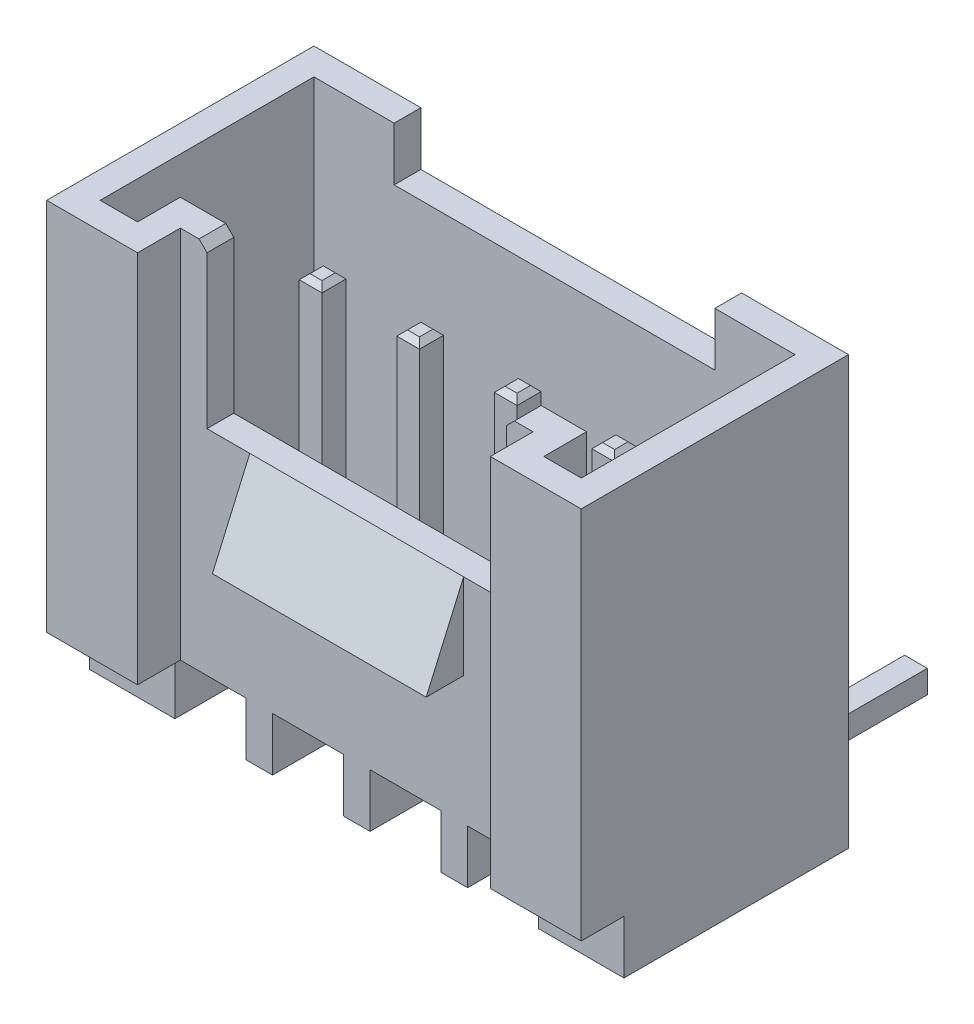
SolidWorks part; units mm, degrees
ref_plane "Plan de face" through (0, 0, 0) normal (0, 0, 1) x (1, 0, 0)
ref_plane "Plan de dessus" through (0, 0, 0) normal (0, 1, 0) x (1, 0, 0)
ref_plane "Plan de droite" through (0, 0, 0) normal (1, 0, 0) x (0, 0, -1)
sketch "Esquisse1" plane through (0, 0, 0) normal (0, 1, 0) x (1, 0, 0)
  line L1 (0, 0) -> (10, 0)
  line L2 (0, 0) -> (0, 5)
  line L3 (0, 5) -> (10, 5)
  line L4 (10, 0) -> (10, 5)
  dimension "D1" = 5
  dimension "D2" = 10
extrude "Boss.-Extru.1" add sketch "Esquisse1" along normal blind 8
sketch "Esquisse2" plane through (0, 8, 0) normal (0, 1, 0) x (1, 0, 0)
  line L0 (0, 0) -> (10, 0) construction
  line L1 (1.7, 0) -> (8.3, 0)
  line L2 (1.7, 0) -> (1.7, 0.8)
  line L3 (1.7, 0.8) -> (8.3, 0.8)
  line L4 (8.3, 0) -> (8.3, 0.8)
  line L5 (0, 5) -> (0, 0) construction
  line L6 (10, 0) -> (10, 5) construction
  dimension "D1" = 1.7
  dimension "D2" = 1.7
  dimension "D3" = 0.8
extrude "Enlèv. mat.-Extru.1" cut sketch "Esquisse2" against normal blind 8
sketch "Esquisse4" plane through (0, 8, 0) normal (0, 1, 0) x (1, 0, 0)
  line L16 (0.5, 0.5) -> (1.2, 0.5)
  line L17 (1.2, 0.5) -> (1.2, 1.3)
  line L18 (1.2, 1.3) -> (8.8, 1.3)
  line L19 (8.8, 1.3) -> (8.8, 0.5)
  line L20 (8.8, 0.5) -> (9.5, 0.5)
  line L21 (9.5, 0.5) -> (9.5, 4.5)
  line L22 (9.5, 4.5) -> (0.5, 4.5)
  line L23 (0.5, 4.5) -> (0.5, 0.5)
  line L24 (0.5, 0.5) -> (1.2, 0.5)
  line L25 (1.2, 0.5) -> (1.2, 1.3)
  line L26 (1.2, 1.3) -> (8.8, 1.3)
  line L27 (8.8, 1.3) -> (8.8, 0.5)
  line L28 (8.8, 0.5) -> (9.5, 0.5)
  line L29 (9.5, 0.5) -> (9.5, 4.5)
  line L30 (9.5, 4.5) -> (0.5, 4.5)
  line L31 (0.5, 4.5) -> (0.5, 0.5)
  dimension "D1" = 0.5
extrude "Enlèv. mat.-Extru.2" cut sketch "Esquisse4" against normal blind 6.5
sketch "Esquisse5" plane through (0, 8, 0) normal (0, 1, 0) x (1, 0, 0)
  line L0 (10, 5) -> (0, 5) construction
  line L1 (2, 5) -> (8, 5)
  line L2 (2, 5) -> (2, 4.5)
  line L3 (2, 4.5) -> (8, 4.5)
  line L4 (8, 5) -> (8, 4.5)
  line L5 (9.5, 4.5) -> (0.5, 4.5) construction
  line L6 (10, 0) -> (10, 5) construction
  line L7 (0, 5) -> (0, 0) construction
  dimension "D1" = 2
  dimension "D2" = 2
extrude "Enlèv. mat.-Extru.3" cut sketch "Esquisse5" against normal blind 1
sketch "Esquisse6" plane through (0, 8, 0) normal (0, 1, 0) x (1, 0, 0)
  line L0 (1.2, 1.3) -> (8.8, 1.3) construction
  line L1 (2.2, 1.3) -> (7.8, 1.3)
  line L2 (2.2, 1.3) -> (2.2, 0.8)
  line L3 (2.2, 0.8) -> (7.8, 0.8)
  line L4 (7.8, 1.3) -> (7.8, 0.8)
  line L5 (8.3, 0.8) -> (1.7, 0.8) construction
  line L6 (10, 0) -> (10, 5) construction
  line L7 (0, 5) -> (0, 0) construction
  dimension "D1" = 2.2
  dimension "D2" = 2.2
extrude "Enlèv. mat.-Extru.4" cut sketch "Esquisse6" against normal blind 3
sketch "Esquisse7" plane through (10, 0, 0) normal (1, 0, 0) x (0, 0, -1)
  line L1 (0, 0) -> (0.8, 0)
  line L2 (0, 0) -> (0, 1)
  line L3 (0, 1) -> (0.8, 1)
  line L4 (0.8, 0) -> (0.8, 1)
  dimension "D1" = 0.8
  dimension "D2" = 1
extrude "Enlèv. mat.-Extru.5" cut sketch "Esquisse7" against normal blind 10
sketch "Esquisse8" plane through (0, 0, 0) normal (0, -1, 0) x (1, 0, 0)
  line L0 (10, -0.8) -> (0, -0.8) construction
  line L1 (1.6, -0.8) -> (8.4, -0.8)
  line L2 (1.6, -0.8) -> (1.6, -5)
  line L3 (1.6, -5) -> (8.4, -5)
  line L4 (8.4, -0.8) -> (8.4, -5)
  line L5 (10, -5) -> (0, -5) construction
  line L6 (0, -5) -> (0, -0.8) construction
  line L7 (10, -0.8) -> (10, -5) construction
  dimension "D1" = 1.6
  dimension "D2" = 1.6
extrude "Enlèv. mat.-Extru.6" cut sketch "Esquisse8" against normal blind 1
sketch "Esquisse9" plane through (1.6, 0, 0) normal (1, 0, 0) x (0, 0, -1)
  line L0 (5, 1) -> (0.8, 1) construction
  line L1 (4.7, 1) -> (3.9, 0.2)
  line L2 (3.9, 0.2) -> (1.9, 0.2)
  line L3 (1.9, 0.2) -> (1.1, 1)
  line L4 (0.8, 0) -> (5, 0) construction
  line L5 (4.7, 1) -> (1.1, 1)
  dimension "D1" = 45
  dimension "D2" = 45
  dimension "D3" = 0.2
  dimension "D4" = 0.3
  dimension "D5" = 0.3
extrude "Boss.-Extru.2" add sketch "Esquisse9" along normal blind 6.8
ref_plane "Plan1" through (5, 0, 0) normal (1, 0, 0) x (0, 0, -1)
sketch "Esquisse11" plane through (5, 0, 0) normal (1, 0, 0) x (0, 0, -1)
  line L0 (0.8, 5) -> (0.1, 3.4)
  line L1 (0.1, 3.4) -> (0.8, 3.4)
  line L2 (0.8, 1) -> (0.8, 8) construction
  line L3 (0.8, 3.4) -> (0.8, 5)
  dimension "D1" = 1.6
  dimension "D2" = 0.7
extrude "Boss.-Extru.3" add sketch "Esquisse11" along normal blind 2 and the other way blind 2
ref_plane "Plan2" through (0, 1, 0) normal (0, 1, 0) x (1, 0, 0)
sketch "Esquisse12" plane through (0, 1, 0) normal (0, 1, 0) x (1, 0, 0)
  line L0 (8.3, 0.8) -> (1.7, 0.8) construction
  line L1 (1.6, 5) -> (8.4, 5) construction
  line L2 (3, 0.8) -> (7, 0.8) construction
  line L3 (4.75, 0.8) -> (5.25, 0.8)
  line L4 (4.75, 0.8) -> (4.75, 5)
  line L5 (4.75, 5) -> (5.25, 5)
  line L6 (5.25, 0.8) -> (5.25, 5)
  line L8 (2.925, 0.8) -> (3.425, 0.8)
  line L9 (2.925, 0.8) -> (2.925, 5)
  line L10 (2.925, 5) -> (3.425, 5)
  line L11 (3.425, 0.8) -> (3.425, 5)
  line L12 (6.575, 0.8) -> (7.075, 0.8)
  line L13 (6.575, 0.8) -> (6.575, 5)
  line L14 (6.575, 5) -> (7.075, 5)
  line L15 (7.075, 0.8) -> (7.075, 5)
  line L16 (3.175, 0.8) -> (3.175, 5) construction
  line L17 (6.825, 0.8) -> (6.825, 5) construction
  point P0 (5, 0.8)
  point P1 (5, 5)
  dimension "D1" = 0.5
  dimension "D2" = 0.25
  dimension "D3" = 0.5
  dimension "D4" = 0.5
  dimension "D5" = 0.25
  dimension "D6" = 0.25
  dimension "D7" = 1.575
  dimension "D8" = 1.575
extrude "Boss.-Extru.4" add sketch "Esquisse12" against normal blind 1
chamfer "Chanfrein1" distance 0.15 angle 45 2 edges at (2.2, 8, -1.05) (7.8, 8, -1.05)
sketch "Esquisse13" plane through (0, 0.2, 0) normal (0, -1, 0) x (1, 0, 0)
  line L0 (5, -0.8) -> (5, -5) construction
  line L1 (2.05, -2.675) -> (2.475, -2.675)
  line L2 (2.05, -2.675) -> (2.05, -3.125)
  line L3 (2.05, -3.125) -> (2.475, -3.125)
  line L4 (2.475, -2.675) -> (2.475, -3.125)
  line L5 (4.3, -3.125) -> (3.875, -3.125)
  line L6 (3.875, -2.675) -> (3.875, -3.125)
  line L7 (4.3, -2.675) -> (4.3, -3.125)
  line L8 (4.3, -2.675) -> (3.875, -2.675)
  line L9 (4.75, -0.8) -> (5.25, -0.8) construction
  line L10 (5.25, -5) -> (4.75, -5) construction
  line L11 (1.6, -0.8) -> (1.6, -5) construction
  line L12 (2.925, -5) -> (2.925, -0.8) construction
  line L14 (2.05, -2.9) -> (2.475, -2.9) construction
  line L15 (2.925, -1.9) -> (1.6, -1.9) construction
  line L16 (3.175, -0.8) -> (3.175, -5) construction
  line L17 (2.925, -0.8) -> (3.425, -0.8) construction
  line L18 (3.425, -5) -> (2.925, -5) construction
  line L19 (5.7, -3.125) -> (6.125, -3.125)
  line L20 (5.7, -2.675) -> (5.7, -3.125)
  line L21 (5.7, -2.675) -> (6.125, -2.675)
  line L22 (6.125, -2.675) -> (6.125, -3.125)
  line L23 (7.525, -2.675) -> (7.525, -3.125)
  line L24 (7.95, -3.125) -> (7.525, -3.125)
  line L25 (7.95, -2.675) -> (7.95, -3.125)
  line L26 (7.95, -2.675) -> (7.525, -2.675)
  dimension "D1" = 0.45
  dimension "D2" = 0.45
  dimension "D3" = 0.45
  dimension "D4" = 1
extrude "Boss.-Extru.5" add sketch "Esquisse13" along normal blind 0.5 and the other way blind 6.3
chamfer "Chanfrein2" distance 0.1 angle 45 16 edges at (7.7375, 6.5, -2.675) (7.95, 6.5, -2.9) (7.525, 6.5, -2.9) (7.7375, 6.5, -3.125) (5.9125, 6.5, -2.675) (6.125, 6.5, -2.9) (5.9125, 6.5, -3.125) (5.7, 6.5, -2.9) (4.0875, 6.5, -2.675) (4.3, 6.5, -2.9) (4.0875, 6.5, -3.125) (3.875, 6.5, -2.9) (2.05, 6.5, -2.9) (2.2625, 6.5, -3.125) (2.475, 6.5, -2.9) (2.2625, 6.5, -2.675)
sketch "Esquisse14" plane through (0, 0, -3.125) normal (0, 0, -1) x (-1, 0, 0)
  line L0 (-7.525, 0.2) -> (-7.525, -0.3) construction
  line L1 (-7.95, -0.3) -> (-7.525, -0.3)
  line L2 (-7.95, -0.3) -> (-7.95, 0.13)
  line L3 (-7.95, 0.13) -> (-7.525, 0.13)
  line L4 (-7.525, -0.3) -> (-7.525, 0.13)
  line L5 (-6.825, 0) -> (-6.825, 1.119) construction
  line L6 (-7.075, 0) -> (-6.575, 0) construction
  line L7 (-5, 0) -> (-5, 1.119) construction
  line L8 (-5.25, 0) -> (-4.75, 0) construction
  line L9 (-5.7, -0.3) -> (-6.125, -0.3)
  line L10 (-6.125, -0.3) -> (-6.125, 0.13)
  line L11 (-5.7, -0.3) -> (-5.7, 0.13)
  line L12 (-5.7, 0.13) -> (-6.125, 0.13)
  line L13 (-4.3, -0.3) -> (-3.875, -0.3)
  line L14 (-4.3, -0.3) -> (-4.3, 0.13)
  line L15 (-4.3, 0.13) -> (-3.875, 0.13)
  line L16 (-3.875, -0.3) -> (-3.875, 0.13)
  line L17 (-2.05, -0.3) -> (-2.475, -0.3)
  line L18 (-2.475, -0.3) -> (-2.475, 0.13)
  line L19 (-2.05, -0.3) -> (-2.05, 0.13)
  line L20 (-2.05, 0.13) -> (-2.475, 0.13)
  dimension "D1" = 0.43
extrude "Boss.-Extru.6" add sketch "Esquisse14" along normal blind 5.5
fillet "Congé1" radius 0.1 8 edges at (2.2625, 0.13, -3.125) (4.0875, 0.13, -3.125) (5.9125, 0.13, -3.125) (7.7375, 0.13, -3.125) (2.2625, -0.3, -2.675) (4.0875, -0.3, -2.675) (5.9125, -0.3, -2.675) (7.7375, -0.3, -2.675)
chamfer "Chanfrein3" distance 0.1 angle 45 16 edges at (2.2625, -0.3, -8.625) (2.475, -0.085, -8.625) (2.2625, 0.13, -8.625) (2.05, -0.085, -8.625) (4.0875, 0.13, -8.625) (3.875, -0.085, -8.625) (4.0875, -0.3, -8.625) (4.3, -0.085, -8.625) (5.9125, -0.3, -8.625) (6.125, -0.085, -8.625) (5.9125, 0.13, -8.625) (5.7, -0.085, -8.625) (7.7375, 0.13, -8.625) (7.525, -0.085, -8.625) (7.7375, -0.3, -8.625) (7.95, -0.085, -8.625)
